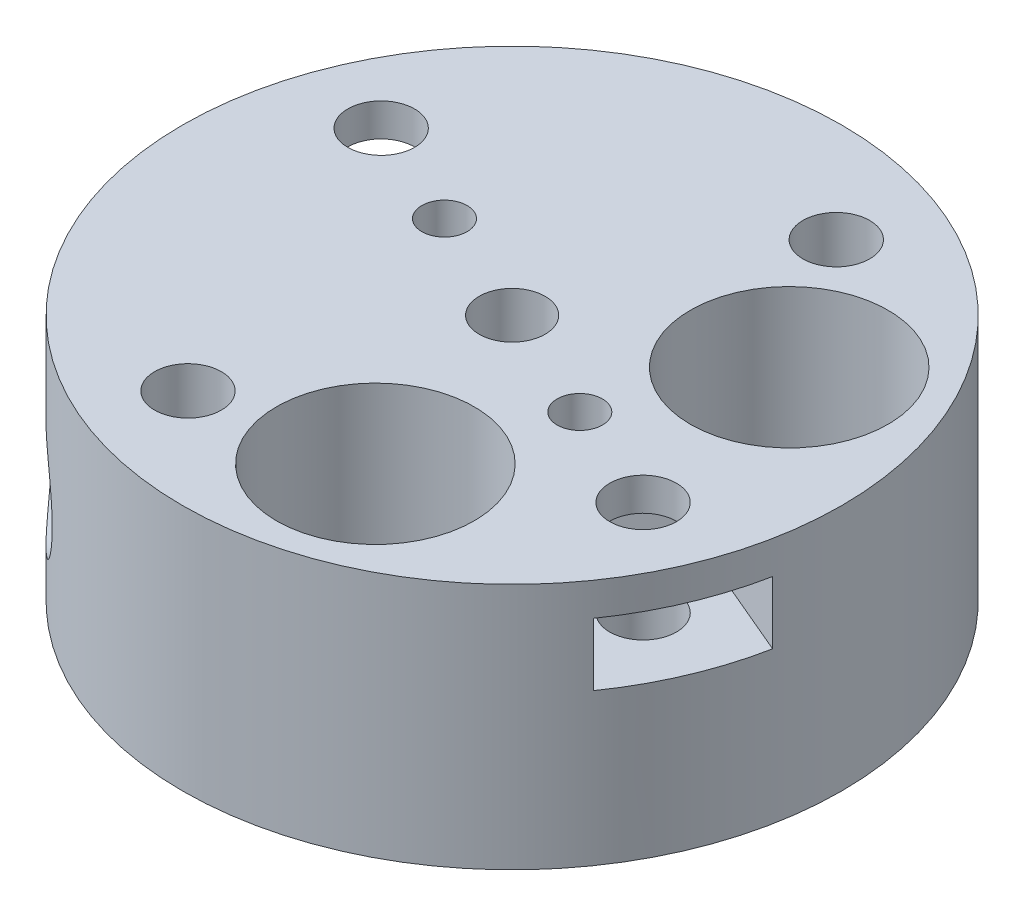
SolidWorks part; units mm, degrees
ref_plane "Front Plane" through (0, 0, 0) normal (0, 0, 1) x (1, 0, 0)
ref_plane "Top Plane" through (0, 0, 0) normal (0, 1, 0) x (1, 0, 0)
ref_plane "Right Plane" through (0, 0, 0) normal (1, 0, 0) x (0, 0, -1)
sketch "Sketch1" plane through (0, 0, 0) normal (0, 1, 0) x (1, 0, 0)
  circle A0 centre (0, 0) radius 20
  dimension "D1" = 40
extrude "Boss-Extrude1" add sketch "Sketch1" along normal mid plane 15
sketch "Sketch4" plane through (0, -7.5, 0) normal (0, -1, 0) x (1, 0, 0)
  circle A0 centre (0, 0) radius 5.125
  dimension "D1" = 10.25
extrude "Cut-Extrude2" cut sketch "Sketch4" against normal offset from surface (12.15 mm away) 2.85 up to face at (0, 7.5, 20)
sketch "Sketch5" plane through (0, 7.5, 0) normal (0, 1, 0) x (1, 0, 0)
  circle A0 centre (0, 0) radius 2
  dimension "D1" = 4
extrude "Cut-Extrude3" cut sketch "Sketch5" against normal through all both and the other way through all
sketch "Sketch2" plane through (0, 7.5, 0) normal (0, 1, 0) x (1, 0, 0)
  line L0 (0, 0) -> (0, 20) construction
  line L1 (0, 0) -> (-13.8076, 5.861) construction
  circle A0 centre (0, 0) radius 20 construction
  circle A1 centre (-13.8076, 5.861) radius 2.025
  dimension "D1" = 4.05
  dimension "D2" = 15
  dimension "D3" = 67
extrude "Cut-Extrude1" cut sketch "Sketch2" against normal through all
pattern_circular "CirPattern1" count 4 over 360 about axis through (0, 7.5, 0) along (0, 1, 0) of "Cut-Extrude1"
sketch "Sketch6" plane through (0, 0, 0) normal (0, 0, 1) x (1, 0, 0)
  line L0 (0, 7.5) -> (0, -7.5) construction
  line L1 (20, 7.5) -> (-20, 7.5) construction
  line L2 (-20, -7.5) -> (20, -7.5) construction
  line L3 (-20, 4.65) -> (20, 4.65) construction
  line L4 (-20, 7.5) -> (-20, -7.5) construction
  line L5 (20, -7.5) -> (20, 7.5) construction
  circle A0 centre (0, -1.35) radius 1.525
  dimension "D1" = 3.05
  dimension "D2" = 2.85
  dimension "D3" = 6
extrude "Cut-Extrude4" cut sketch "Sketch6" against normal through all
sketch "Sketch7" plane through (0, 0, 0) normal (0, 0, 1) x (1, 0, 0)
  circle A0 centre (0, -1.35) radius 3.25
  dimension "D1" = 6.5
extrude "Cut-Extrude5" cut sketch "Sketch7" along normal blind 8 from offset 20 offset against normal yes
sketch "Sketch9" plane through (0, 0, 0) normal (0, 0, 1) x (1, 0, 0)
  line L0 (20, -7.5) -> (20, 7.5) construction
  line L1 (0, -4.9873) -> (3.15, -3.1687) construction
  line L2 (3.15, -3.1687) -> (3.15, 0.4687)
  line L3 (3.15, 0.4687) -> (0, 2.2873)
  line L4 (0, 2.2873) -> (-3.15, 0.4687)
  line L5 (-3.15, 0.4687) -> (-3.15, -3.1687)
  line L6 (-3.15, -3.1687) -> (0, -4.9873) construction
  line L7 (3.15, -3.1687) -> (-3.15, -3.1687) construction
  line L8 (3.15, -3.1687) -> (3.15, -7.6851)
  line L9 (-3.15, -3.1687) -> (-3.15, -7.6851)
  line L10 (3.15, -7.6851) -> (-3.15, -7.6851)
  circle A0 centre (0, -1.35) radius 3.15 construction
  dimension "D1" = 6.3
extrude "Cut-Extrude11" cut sketch "Sketch9" against normal blind 2.9 from offset 6.5 offset against normal yes
pattern_circular "CirPattern2" count 2 every 135 about axis through (0, 7.5, 0) along (0, 1, 0) of "Cut-Extrude4", "Cut-Extrude5", "Cut-Extrude11"
sketch "Sketch8" plane through (0, 0, 0) normal (0, 1, 0) x (1, 0, 0)
  line L0 (0, 0) -> (-13.8076, 5.861) construction
  line L1 (-9.3965, 3.9886) -> (-9.9805, 8.7449)
  line L2 (-9.9805, 8.7449) -> (-14.3916, 10.6173)
  line L3 (-14.3916, 10.6173) -> (-18.2186, 7.7334) construction
  line L4 (-18.2186, 7.7334) -> (-17.6346, 2.9771) construction
  line L5 (-17.6346, 2.9771) -> (-13.2236, 1.1047)
  line L6 (-13.2236, 1.1047) -> (-9.3965, 3.9886)
  line L7 (-14.3916, 10.6173) -> (-17.6346, 2.9771) construction
  line L8 (-14.3916, 10.6173) -> (-19.5699, 12.8153)
  line L9 (-17.6346, 2.9771) -> (-22.813, 5.1751)
  line L10 (-19.5699, 12.8153) -> (-22.813, 5.1751)
  circle A0 centre (-13.8076, 5.861) radius 4.15 construction
  dimension "D1" = 8.3
extrude "Cut-Extrude7" cut sketch "Sketch8" against normal blind 3.8 from offset 5.5
pattern_circular "CirPattern3" count 2 over 360 about axis through (0, 7.5, 0) along (0, 1, 0) of "Cut-Extrude7"
sketch "Sketch10" plane through (0, 7.5, 0) normal (0, 1, 0) x (1, 0, 0)
  line L0 (0, 0) -> (0, -20) construction
  line L1 (0, 0) -> (3.6546, -11.9538) construction
  circle A0 centre (0, 0) radius 20 construction
  circle A1 centre (3.6546, -11.9538) radius 6
  dimension "D1" = 12
  dimension "D2" = 17
  dimension "D3" = 12.5
extrude "Cut-Extrude12" cut sketch "Sketch10" against normal through all both and the other way through all
pattern_circular "CirPattern4" count 2 every 100 about axis through (0, 7.5, 0) along (0, 1, 0) of "Cut-Extrude12"
sketch "Sketch11" plane through (0, 7.5, 0) normal (0, 1, 0) x (1, 0, 0)
  line L0 (0, 0) -> (13.8076, -5.861) construction
  circle A0 centre (7.1339, -3.0282) radius 1.375
  circle A1 centre (0, 0) radius 2 construction
  dimension "D1" = 2.75
  dimension "D2" = 7.75
extrude "Cut-Extrude13" cut sketch "Sketch11" against normal through all both and the other way through all
sketch "Sketch13" plane through (0, -7.5, 0) normal (0, -1, 0) x (-1, 0, 0)
  circle A0 centre (-7.1339, -3.0282) radius 2.375
  dimension "D1" = 4.75
extrude "Cut-Extrude24" cut sketch "Sketch13" against normal offset from surface (12 mm away) 3 up to face at (7.1339, 7.5, 4.4032)
pattern_circular "CirPattern5" count 2 over 360 about axis through (0, 7.5, 0) along (0, 1, 0) of "Cut-Extrude13", "Cut-Extrude24"
